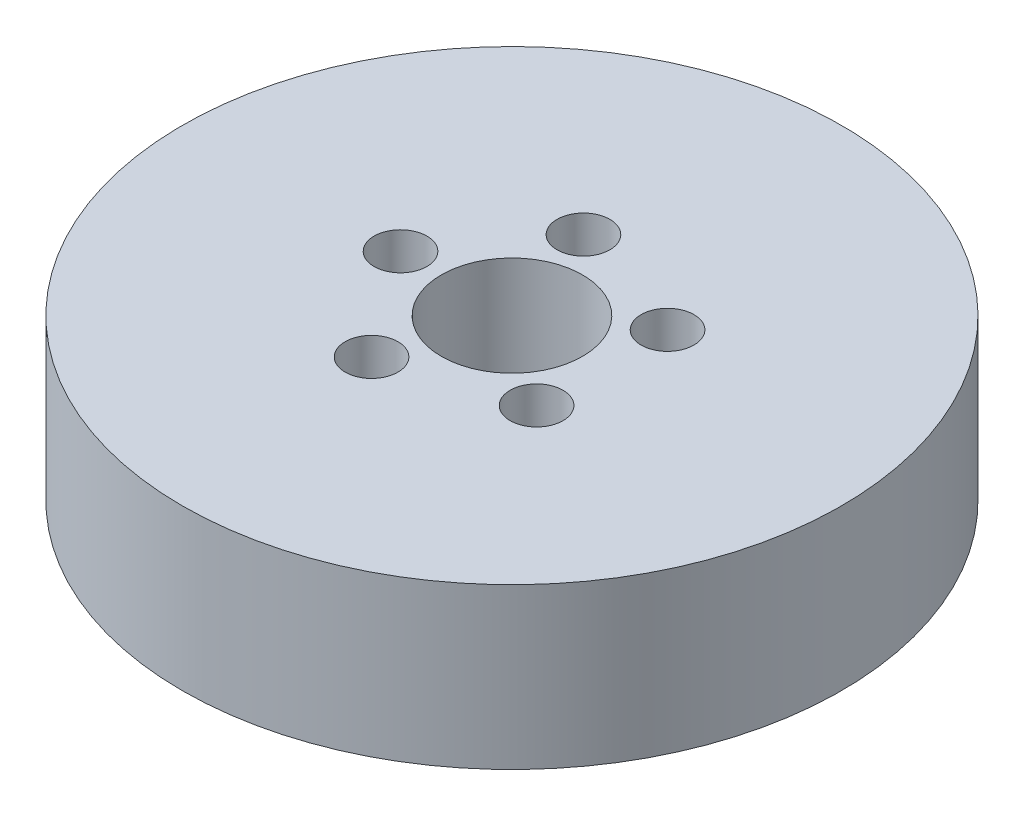
SolidWorks part; units mm, degrees
ref_plane "Front Plane" through (0, 0, 0) normal (0, 0, 1) x (1, 0, 0)
ref_plane "Top Plane" through (0, 0, 0) normal (0, 1, 0) x (1, 0, 0)
ref_plane "Right Plane" through (0, 0, 0) normal (1, 0, 0) x (0, 0, -1)
sketch "Sketch1" plane through (0, 0, 0) normal (0, 1, 0) x (1, 0, 0)
  circle A0 centre (0, 0) radius 35
  dimension "FLANGE_OD" = 70
extrude "Boss-Extrude1" add sketch "Sketch1" along normal blind 17
sketch "Sketch2" plane through (0, 0, 0) normal (0, 1, 0) x (1, 0, 0)
  circle A0 centre (0, 0) radius 7.5
  dimension "BORE_D" = 15
extrude "Cut-Extrude1" cut sketch "Sketch2" along normal through all
sketch "Sketch3" plane through (0, 17, 0) normal (0, 1, 0) x (1, 0, 0)
  circle A0 centre (0, 0) radius 11.8302 construction
  circle A1 centre (-11.8302, 0) radius 2.8053
  dimension "BOLT_D" = 5.6107
  dimension "BOLT_PCD" = 23.6605
extrude "Cut-Extrude2" cut sketch "Sketch3" against normal blind 16.664
pattern_circular "CirPattern1" count 5 over 360 about axis through (0, 0, 0) along (0, 1, 0) of "Cut-Extrude2"
